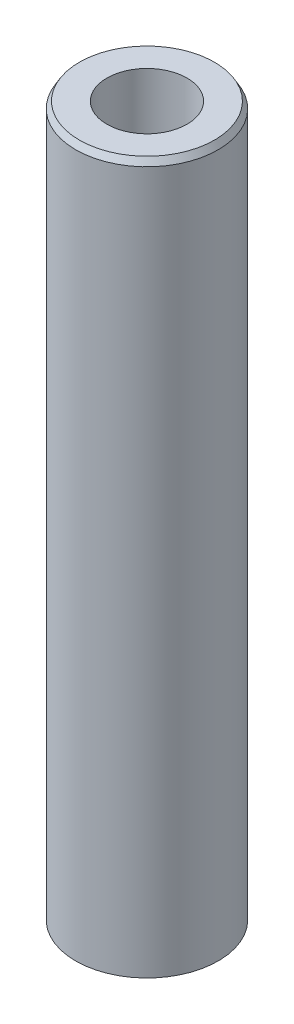
SolidWorks part; units mm, degrees
ref_plane "Front Plane" through (0, 0, 0) normal (0, 0, 1) x (1, 0, 0)
ref_plane "Top Plane" through (0, 0, 0) normal (0, 1, 0) x (1, 0, 0)
ref_plane "Right Plane" through (0, 0, 0) normal (1, 0, 0) x (0, 0, -1)
sketch "Sketch1" plane through (0, 0, 0) normal (0, 1, 0) x (1, 0, 0)
  circle A0 centre (0, 0) radius 60
  dimension "SHAFT_OD" = 120
extrude "Boss-Extrude1" add sketch "Sketch1" along normal blind 600
sketch "Sketch2" plane through (0, 0, 0) normal (0, 1, 0) x (1, 0, 0)
  circle A0 centre (0, 0) radius 33.725
  dimension "BORE_D" = 67.4501
extrude "Cut-Extrude1" cut sketch "Sketch2" along normal through all
chamfer "Chamfer1" distance 5.454 angle 30 2 edges at (0, 600, 60) (0, 0, 60) first distance on face at (0, 600, 60) first distance on face at (0, 0, 33.725)
